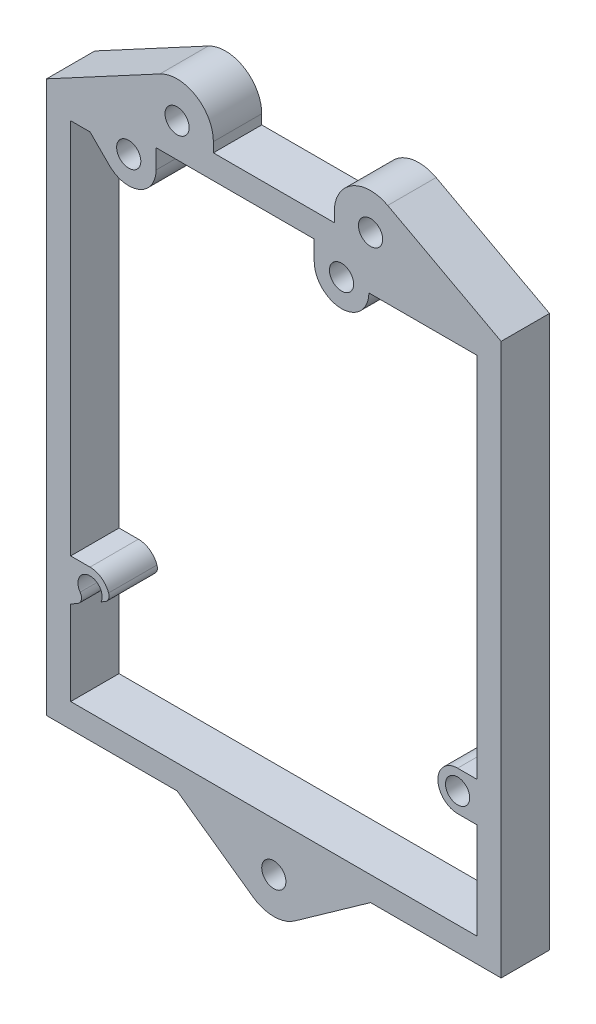
SolidWorks part; units mm, degrees
ref_plane "Front Plane" through (0, 0, 0) normal (0, 0, 1) x (1, 0, 0)
ref_plane "Top Plane" through (0, 0, 0) normal (0, 1, 0) x (1, 0, 0)
ref_plane "Right Plane" through (0, 0, 0) normal (1, 0, 0) x (0, 0, -1)
sketch "Sketch1" plane through (0, 0, 0) normal (0, 0, 1) x (1, 0, 0)
  line L0 (13.97, -3.175) -> (23.9132, -10.2335)
  line L1 (29.4268, -10.2335) -> (39.37, -3.175)
  line L2 (39.37, -3.175) -> (56.515, -3.175)
  line L3 (18.7325, 73.025) -> (18.7325, 71.755)
  line L4 (56.515, 69.215) -> (41.6251, 77.2198)
  line L5 (34.6075, 73.025) -> (34.6075, 71.755)
  line L6 (-3.175, 69.215) -> (11.7149, 77.2198)
  line L7 (34.6075, 71.755) -> (18.7325, 71.755)
  line L36 (53.34, 66.04) -> (53.34, 0) construction
  line L37 (53.34, 0) -> (0, 0) construction
  line L38 (0, 0) -> (0, 66.04) construction
  line L39 (0, 66.04) -> (2.54, 66.04) construction
  line L43 (40.386, 66.04) -> (53.34, 66.04) construction
  line L44 (-3.175, -3.175) -> (56.515, -3.175)
  line L45 (56.515, -3.175) -> (56.515, 69.215)
  line L46 (-3.175, 69.215) -> (-3.175, -3.175)
  line L47 (1.2249, 69.215) -> (-3.175, 69.215)
  line L48 (3.7649, 71.755) -> (1.2249, 69.215)
  line L49 (39.1611, 71.755) -> (3.7649, 71.755)
  line L50 (41.7011, 69.215) -> (39.1611, 71.755)
  line L51 (56.515, 69.215) -> (41.7011, 69.215)
  line L52 (-3.175, -3.175) -> (13.97, -3.175)
  line L53 (56.515, -3.175) -> (56.515, 69.215)
  line L54 (-3.175, 69.215) -> (-3.175, -3.175)
  line L60 (53.34, 66.04) -> (53.34, 17.8275)
  line L61 (53.34, 0) -> (0, 0)
  line L62 (0, 0) -> (0, 11.0938)
  line L63 (0, 66.04) -> (2.54, 66.04)
  line L64 (26.67, -3.175) -> (26.67, 77.2177) construction
  line L66 (11.2075, 68.58) -> (31.9725, 68.58)
  line L67 (40.386, 66.04) -> (53.34, 66.04)
  line L68 (50.8, 17.8275) -> (53.34, 17.8275)
  line L69 (50.8, 12.6525) -> (53.34, 12.6525)
  line L70 (53.34, 12.6525) -> (53.34, 0)
  line L71 (2.54, 16.5575) -> (0, 16.5575)
  line L72 (5.1275, 13.97) -> (3.9948, 13.3346)
  line L73 (2.3238, 12.3973) -> (0, 11.0938)
  line L74 (0, 16.5575) -> (0, 66.04)
  line L75 (5.08, 63.5065) -> (2.54, 66.04)
  line L76 (11.2075, 66.04) -> (11.2075, 68.58)
  line L77 (39.1475, 66.04) -> (40.386, 66.04)
  line L78 (31.9725, 66.04) -> (31.9725, 68.58)
  circle A0 centre (35.56, 66.04) radius 1.5875 construction
  circle A1 centre (7.62, 66.04) radius 1.5875 construction
  circle A2 centre (2.54, 13.97) radius 1.5875 construction
  circle A3 centre (50.8, 15.24) radius 1.5875 construction
  circle A4 centre (35.56, 66.04) radius 1.5875
  circle A5 centre (7.62, 66.04) radius 1.5875
  arc A6 (3.9948, 13.3346) -> (2.3238, 12.3973) centre (2.54, 13.97) ccw
  circle A7 centre (50.8, 15.24) radius 1.5875
  arc A8 (5.1275, 13.97) -> (2.54, 16.5575) centre (2.54, 13.97) ccw
  arc A9 (50.8, 17.8275) -> (50.8, 12.6525) centre (50.8, 15.24) ccw
  arc A10 (5.08, 63.5065) -> (11.2075, 66.04) centre (7.62, 66.04) ccw
  circle A11 centre (2.54, 13.97) radius 2.5875 construction
  circle A12 centre (2.54, 13.97) radius 1.5875 construction
  arc A13 (31.9725, 66.04) -> (39.1475, 66.04) centre (35.56, 66.04) ccw
  circle A14 centre (26.67, -6.35) radius 1.5875
  circle A15 centre (35.56, 66.04) radius 3.5875 construction
  circle A16 centre (7.62, 66.04) radius 3.5875 construction
  arc A17 (23.9132, -10.2335) -> (29.4268, -10.2335) centre (26.67, -6.35) ccw
  circle A18 centre (39.37, 73.025) radius 1.5875
  arc A19 (41.6251, 77.2198) -> (34.6075, 73.025) centre (39.37, 73.025) ccw
  circle A20 centre (13.97, 73.025) radius 1.5875
  arc A22 (11.7149, 77.2198) -> (18.7325, 73.025) centre (13.97, 73.025) cw
  circle A23 centre (26.67, -6.35) radius 4.7625 construction
  circle A24 centre (13.97, 73.025) radius 4.7625 construction
  point P34 (53.3875, 15.24)
  point P37 (6.1275, 13.97)
  point P41 (4.0581, 14.4341)
  point P47 (11.2075, 66.04)
  point P54 (39.1475, 66.04)
  point P58 (26.67, -9.525)
  point P64 (31.4325, -9.525)
  point P69 (26.67, 71.755)
  point P71 (39.37, 73.025)
  point P74 (50.4825, 73.025)
  point P75 (12.3825, 73.025)
  point P78 (31.4325, -6.35)
  dimension "D4" = 6.35
  dimension "D8" = 3.175
  dimension "D5" = 3.175
  dimension "D7" = 12.7
  dimension "D9" = 12.7
  dimension "D1" = 3.175
  dimension "D2" = 1
  dimension "D3" = 2
  dimension "D12" = 3.175
extrude "Boss-Extrude1" add sketch "Sketch1" along normal blind 6.35
fillet "Fillet1" radius 1 2 edges at (2.3238, 12.3973, 3.175) (5.1275, 13.97, 3.175)
